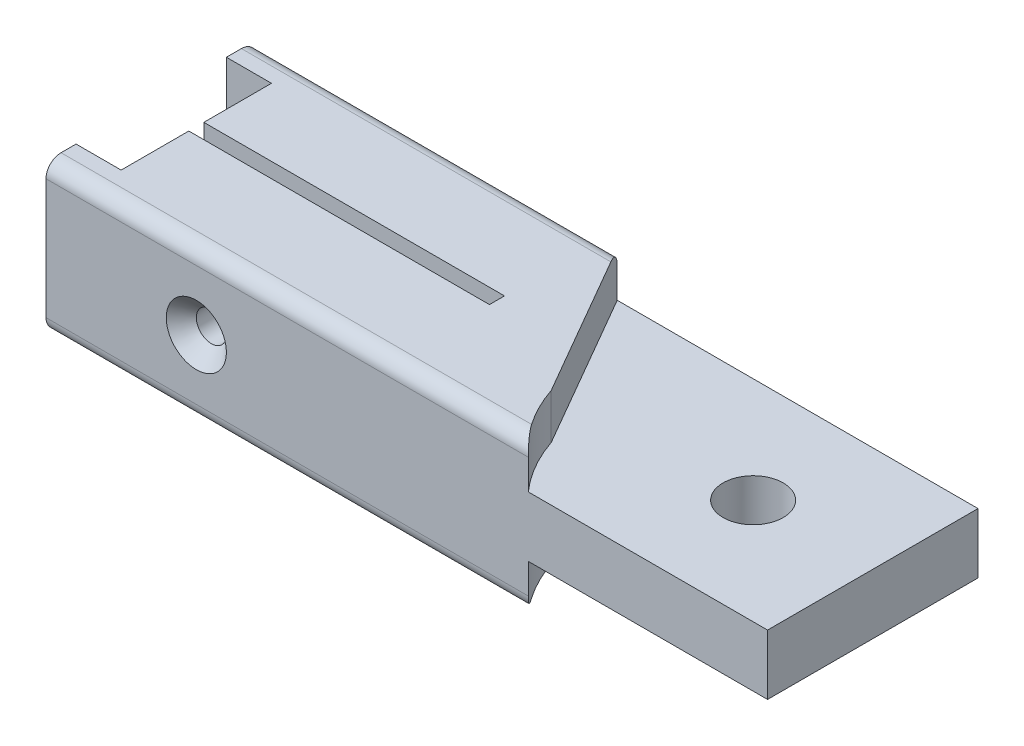
SolidWorks part; units mm, degrees
ref_plane "前视基准面" through (0, 0, 0) normal (0, 0, 1) x (1, 0, 0)
ref_plane "上视基准面" through (0, 0, 0) normal (0, 1, 0) x (1, 0, 0)
ref_plane "右视基准面" through (0, 0, 0) normal (1, 0, 0) x (0, 0, -1)
sketch "草图1" plane through (0, 0, 0) normal (1, 0, 0) x (0, 0, -1)
  line L1 (3.5, -2.5) -> (-3.5, -2.5)
  line L2 (3.5, -2.5) -> (3.5, 2.5)
  line L3 (3.5, 2.5) -> (-3.5, 2.5)
  line L4 (-3.5, -2.5) -> (-3.5, 2.5)
  line L5 (3.5, -2.5) -> (-3.5, 2.5) construction
  line L6 (3.5, 2.5) -> (-3.5, -2.5) construction
  point P0 (0, 0)
  dimension "7" = 7
  dimension "5" = 5
extrude "凸台-拉伸1" add sketch "草图1" along normal blind 24
sketch "草图2" plane through (0, 0, 0) normal (-1, 0, 0) x (0, 0, 1)
  line L1 (2.5, 12.9569) -> (-2.5, 12.9569)
  line L2 (2.5, 12.9569) -> (2.5, -12.9569)
  line L3 (2.5, -12.9569) -> (-2.5, -12.9569)
  line L4 (-2.5, 12.9569) -> (-2.5, -12.9569)
  line L5 (2.5, 12.9569) -> (-2.5, -12.9569) construction
  line L6 (2.5, -12.9569) -> (-2.5, 12.9569) construction
  point P0 (0, 0)
  dimension "D1" = 5
extrude "切除-拉伸1" cut sketch "草图2" against normal blind 1.5 contours L2 L1 L4 L3
sketch "草图3" plane through (1.5, 0, 0) normal (-1, 0, 0) x (0, 0, 1)
  line L1 (-0.25, 6.0281) -> (0.25, 6.0281)
  line L2 (-0.25, 6.0281) -> (-0.25, -6.0281)
  line L3 (-0.25, -6.0281) -> (0.25, -6.0281)
  line L4 (0.25, 6.0281) -> (0.25, -6.0281)
  line L5 (-0.25, 6.0281) -> (0.25, -6.0281) construction
  line L6 (-0.25, -6.0281) -> (0.25, 6.0281) construction
  circle A0 centre (0, 0) radius 2
  dimension "D1" = 0.5
  dimension "4" = 4
extrude "切除-拉伸2" cut sketch "草图3" against normal blind 10 contours A0 | L1 L4 L3 L2
sketch "草图4" plane through (0, -2.5, 0) normal (0, -1, 0) x (1, 0, 0)
  line L0 (12, -3.5) -> (16.0415, 3.5)
  line L1 (24, -3.5) -> (0, -3.5) construction
  line L2 (24, 3.5) -> (0, 3.5) construction
  line L3 (0, -2.5) -> (0, -3.5) construction
  line L5 (24, -3.5) -> (12, -3.5)
  line L6 (24, -3.5) -> (24, 3.5)
  line L7 (24, 3.5) -> (12, 3.5)
  line L8 (12, -3.5) -> (12, 3.5)
  line M7 (0, -3.5) -> (24, -3.5)
  line M8 (24, -3.5) -> (24, 3.5)
  line M9 (24, 3.5) -> (0, 3.5)
  dimension "D1" = 12
  dimension "60" = 60
extrude "切除-拉伸3" cut sketch "草图4" against normal blind 1.5 contours L0 M7 M8 M9
ref_plane "基准面1" through (0, 0, 0) normal (0, -1, 0) x (-1, 0, 0)
mirror "镜向1" about plane through (0, 0, 0) normal (0, -1, 0) of "切除-拉伸3"
sketch "草图5" plane through (0, 1, 0) normal (0, 1, 0) x (1, 0, 0)
  line L0 (12, 3.5) -> (16.0415, -3.5) construction
  circle A0 centre (20.0207, 0) radius 1
  point P4 (14.0207, 0)
  dimension "D1" = 6
  dimension "2" = 2
extrude "切除-拉伸4" cut sketch "草图5" against normal through all contours A0
sketch "草图7" plane through (0, -2.5, 0) normal (0, -1, 0) x (1, 0, 0)
  circle A0 centre (20.0207, 0) radius 5.2995
extrude "切除-拉伸6" cut sketch "草图7" against normal up to vertex (1.5 mm away)
mirror "镜向2" about plane through (0, 0, 0) normal (0, -1, 0) of "切除-拉伸6"
fillet "圆角2" radius 0.5 4 edges at (6, 2.5, -3.5) (8.0207, 2.5, 3.5) (8.0207, -2.5, 3.5) (6, -2.5, -3.5)
sketch "草图8" plane through (0, 0, 3.5) normal (0, 0, 1) x (1, 0, 0)
  line L0 (0, 2) -> (0, -2) construction
  circle A0 centre (5, 0) radius 0.5
  point P2 (0, 0)
  dimension "D2" = 1
  dimension "D1" = 5
extrude "切除-拉伸7" cut sketch "草图8" against normal through all
chamfer "倒角1" distance 0.5 angle 45 2 edges at (4.5097, -0.0978, 1.9976) (5.5, 0, 3.5)
